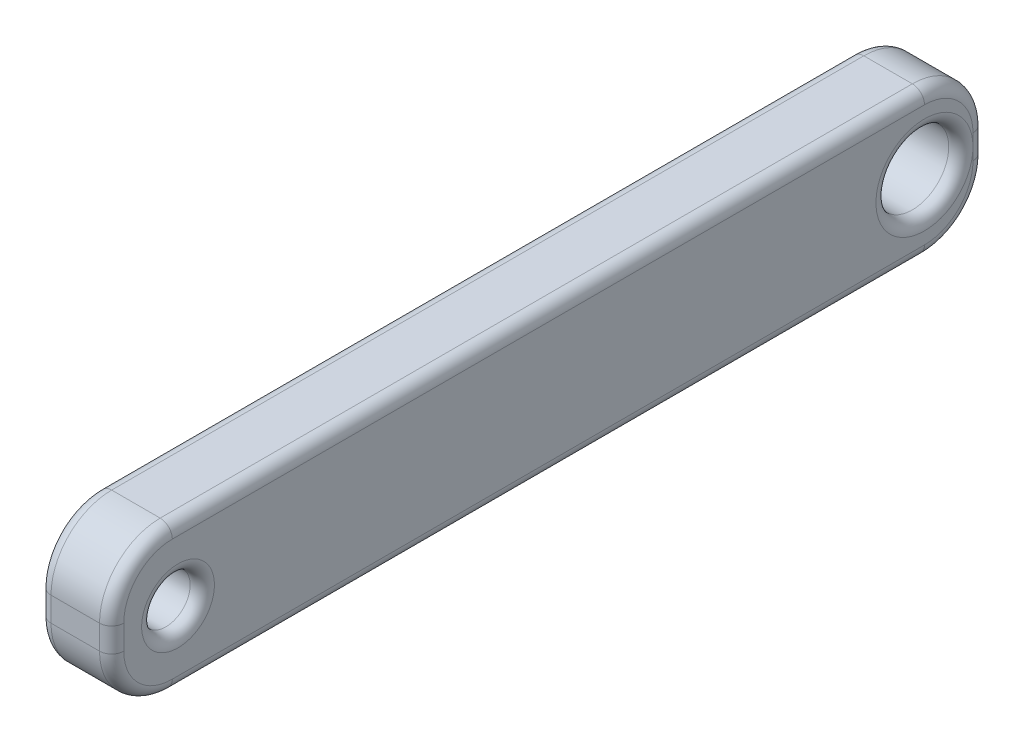
SolidWorks part; units mm, degrees
ref_plane "Front Plane" through (0, 0, 0) normal (0, 0, 1) x (1, 0, 0)
ref_plane "Top Plane" through (0, 0, 0) normal (0, 1, 0) x (1, 0, 0)
ref_plane "Right Plane" through (0, 0, 0) normal (1, 0, 0) x (0, 0, -1)
sketch "Sketch1" plane through (0, 0, 0) normal (1, 0, 0) x (0, 0, -1)
  line L1 (2.5, 0) -> (33.5, 0)
  line L2 (0, 2.5) -> (0, 3.5)
  line L3 (2.5, 6) -> (33.5, 6)
  line L4 (36, 2.5) -> (36, 3.5)
  circle A0 centre (2.7359, 3) radius 1
  arc A2 (36, 3.5) -> (33.5, 6) centre (33.5, 3.5) ccw
  arc A3 (36, 2.5) -> (33.5, 0) centre (33.5, 2.5) cw
  arc A4 (0, 2.5) -> (2.5, 0) centre (2.5, 2.5) ccw
  arc A5 (0, 3.5) -> (2.5, 6) centre (2.5, 3.5) cw
  point P11 (36, 6)
  point P16 (0, 0)
  point P19 (0, 6)
  dimension "D3" = 2
  dimension "D4" = 2.5
  dimension "D1" = 36
  dimension "D2" = 6
extrude "Boss-Extrude1" add sketch "Sketch1" along normal blind 3
sketch "Sketch2" plane through (0, 0, 0) normal (-1, 0, 0) x (0, 0, 1)
  line L0 (-36, 3) -> (0, 3) construction
  line L1 (-36, 2.5) -> (-36, 3.5) construction
  line L2 (0, 3.5) -> (0, 2.5) construction
  circle A0 centre (-33.5, 3) radius 1.5
  dimension "D1" = 3
  dimension "D2" = 2.5
extrude "Cut-Extrude1" cut sketch "Sketch2" against normal blind 10
fillet "Fillet1" radius 0.5 20 edges at (0, 3, -3.7359) (0, 6, -18) (0, 5.2678, -0.7322) (0, 3, 0) (0, 0.7322, -0.7322) (0, 0, -18) (0, 0.7322, -35.2678) (0, 3, -36) (0, 5.2678, -35.2678) (0, 3, -32) (3, 3, -3.7359) (3, 3, -36) (3, 0.7322, -35.2678) (3, 0, -18) (3, 0.7322, -0.7322) (3, 3, 0) (3, 5.2678, -0.7322) (3, 6, -18) (3, 5.2678, -35.2678) (3, 3, -35)
